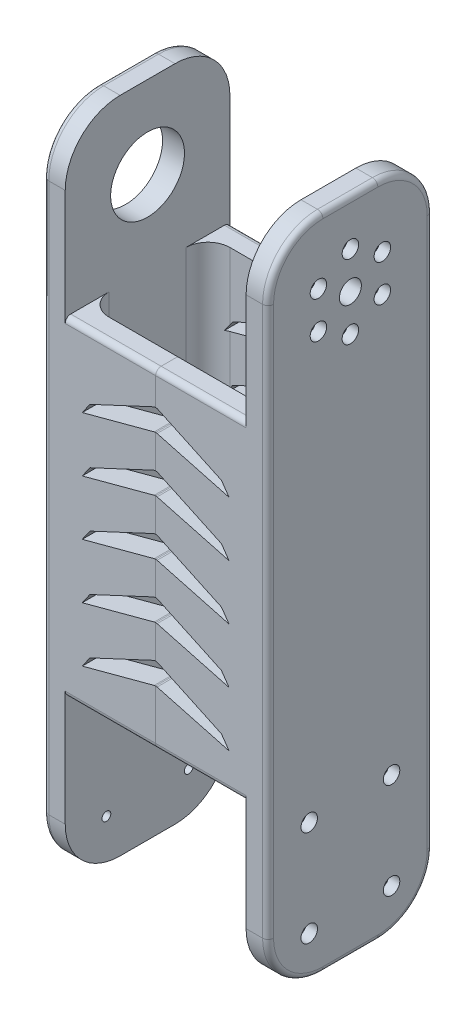
SolidWorks part; units mm, degrees
material "PETG-CF"
ref_plane "前视基准面" through (0, 0, 0) normal (0, 0, 1) x (1, 0, 0)
ref_plane "上视基准面" through (0, 0, 0) normal (0, 1, 0) x (1, 0, 0)
ref_plane "右视基准面" through (0, 0, 0) normal (1, 0, 0) x (0, 0, -1)
other "Configuration Table"
sketch "草图1" plane through (0, 0, 0) normal (1, 0, 0) x (0, 0, -1)
  line L1 (30, -120) -> (-30, -120)
  line L2 (30, -120) -> (30, 120)
  line L3 (30, 120) -> (-30, 120)
  line L4 (-30, -120) -> (-30, 120)
  line L5 (30, -120) -> (-30, 120) construction
  line L6 (30, 120) -> (-30, -120) construction
  point P0 (0, 0)
  dimension "D1" = 240
  dimension "D2" = 60
extrude "凸台-拉伸1" add sketch "草图1" along normal blind 8
sketch "草图2" plane through (8, 0, 0) normal (1, 0, 0) x (0, 0, -1)
  line L1 (30, 120) -> (-30, 120) construction
  circle A12 centre (0, 90) radius 13.45
  point P6 (0, 120)
  point P26 (0, 90)
  dimension "D11" = 26.9
  dimension "D2" = 30
extrude "切除-拉伸1" cut sketch "草图2" against normal through all
sketch "草图3" plane through (8, 0, 0) normal (1, 0, 0) x (0, 0, -1)
  line L0 (-30, 120) -> (-30, -120) construction
  line L1 (-22, -60) -> (-30, -60)
  line L2 (-22, -60) -> (-22, 60)
  line L3 (-22, 60) -> (-30, 60)
  line L4 (-30, -60) -> (-30, 60)
  line L5 (-22, -60) -> (-30, 60) construction
  line L6 (-22, 60) -> (-30, -60) construction
  line L7 (30, -60) -> (22, -60)
  line L8 (30, -60) -> (30, 60)
  line L9 (30, 60) -> (22, 60)
  line L10 (22, -60) -> (22, 60)
  line L11 (30, -60) -> (22, 60) construction
  line L12 (30, 60) -> (22, -60) construction
  line L13 (30, -120) -> (30, 120) construction
  line L14 (30, 120) -> (-30, 120) construction
  line L15 (-30, -120) -> (30, -120) construction
  point P0 (-26, 0)
  point P5 (26, 0)
  dimension "D1" = 60
  dimension "D2" = 60
  dimension "D3" = 60
  dimension "D4" = 60
  dimension "D5" = 8
  dimension "D6" = 8
extrude "凸台-拉伸2" add sketch "草图3" along normal blind 65.9
sketch "草图4" plane through (73.9, 0, 0) normal (1, 0, 0) x (0, 0, -1)
  line L0 (30, -120) -> (-30, 120) construction
  line L1 (30, -120) -> (-30, -120)
  line L2 (30, -120) -> (30, 120)
  line L3 (30, 120) -> (-30, 120)
  line L4 (-30, -120) -> (-30, 120)
  line L5 (30, -120) -> (-30, 120) construction
  line L6 (30, 120) -> (-30, -120) construction
  line L7 (30, 120) -> (-30, 120) construction
  point P0 (0, 0)
extrude "凸台-拉伸3" add sketch "草图4" along normal blind 8
fillet "圆角1" radius 20 8 edges at (4, -120, 30) (4, -120, -30) (4, 120, -30) (4, 120, 30) (77.9, 120, -30) (77.9, 120, 30) (77.9, -120, -30) (77.9, -120, 30)
sketch "草图9" plane through (73.9, 0, 0) normal (-1, 0, 0) x (0, 0, 1)
  circle A0 centre (0, 90) radius 19 construction
  circle A2 centre (0, 109) radius 1.6
  circle A3 centre (19, 90) radius 1.6
  circle A4 centre (0, 71) radius 1.6
  circle A5 centre (-19, 90) radius 1.6
  point P14 (0, 90)
  dimension "D1" = 38
  dimension "D2" = 3.2
sketch "草图10" plane through (81.9, 0, 0) normal (1, 0, 0) x (0, 0, -1)
  circle A0 centre (0, 90) radius 4
  circle A1 centre (0, 90) radius 13.5 construction
  circle A2 centre (0, 103.5) radius 1.6
  circle A3 centre (11.6913, 96.75) radius 1.6
  circle A4 centre (11.6913, 83.25) radius 1.6
  circle A5 centre (0, 76.5) radius 1.6
  circle A6 centre (-11.6913, 83.25) radius 1.6
  circle A7 centre (-11.6913, 96.75) radius 1.6
  point P18 (0, 90)
  dimension "D1" = 8
  dimension "D2" = 27
  dimension "D3" = 3.2
  dimension "D4" = 6
extrude "切除-拉伸2" cut sketch "草图10" against normal up to next
sketch "草图15" plane through (73.9, 0, 0) normal (-1, 0, 0) x (0, 0, 1)
  circle A0 centre (0, 90) radius 18
  dimension "D1" = 36
extrude "凸台-拉伸4" add sketch "草图15" along normal blind 9.8
sketch "草图11" plane through (81.9, 0, 0) normal (1, 0, 0) x (0, 0, -1)
  line L1 (15, -105) -> (-15, -105) construction
  line L2 (15, -105) -> (15, -70) construction
  line L3 (15, -70) -> (-15, -70) construction
  line L4 (-15, -105) -> (-15, -70) construction
  line L5 (15, -105) -> (-15, -70) construction
  line L6 (15, -70) -> (-15, -105) construction
  line L7 (-30, 100) -> (-30, -100) construction
  line L8 (30, -100) -> (30, 100) construction
  line L9 (0, -70) -> (0, -105) construction
  line L10 (-15, -87.5) -> (15, -87.5) construction
  line L11 (-22, -60) -> (-30, -60) construction
  circle A0 centre (-15, -70) radius 1.6
  circle A1 centre (15, -70) radius 1.6
  circle A2 centre (15, -105) radius 1.6
  circle A3 centre (-15, -105) radius 1.6
  point P0 (0, -87.5)
  dimension "D5" = 3.2
  dimension "D1" = 10
  dimension "D2" = 15
  dimension "D3" = 15
  dimension "D4" = 35
extrude "切除-拉伸3" cut sketch "草图11" against normal through all
sketch "草图12" plane through (81.9, 0, 0) normal (1, 0, 0) x (0, 0, -1)
  circle A0 centre (0, 103.45) radius 3
  circle A1 centre (0, 90) radius 13.45 construction
  circle A2 centre (11.648, 96.725) radius 3
  circle A3 centre (11.648, 83.275) radius 3
  circle A4 centre (0, 76.55) radius 3
  circle A5 centre (-11.648, 83.275) radius 3
  circle A6 centre (-11.648, 96.725) radius 3
  point P16 (0, 90)
  dimension "D1" = 6
  dimension "D2" = 6
extrude "切除-拉伸4" cut sketch "草图12" against normal blind 4
sketch "草图13" plane through (81.9, 0, 0) normal (1, 0, 0) x (0, 0, -1)
  line L2 (0, -70) -> (0, -105) construction
  line L3 (-15, -87.5) -> (15, -87.5) construction
  circle A0 centre (-15, -70) radius 3
  circle A1 centre (15, -70) radius 3
  circle A2 centre (15, -105) radius 3
  circle A3 centre (-15, -105) radius 3
  dimension "D1" = 6
extrude "切除-拉伸5" cut sketch "草图13" against normal blind 4
sketch "草图14" plane through (0, 0, 0) normal (-1, 0, 0) x (0, 0, 1)
  line L0 (0, -70) -> (0, -105) construction
  line L1 (-15, -87.5) -> (15, -87.5) construction
  circle A0 centre (-15, -70) radius 3
  circle A1 centre (15, -70) radius 3
  circle A2 centre (15, -105) radius 3
  circle A3 centre (-15, -105) radius 3
  dimension "D1" = 6
extrude "切除-拉伸6" cut sketch "草图14" against normal blind 4
extrude "切除-拉伸7" cut sketch "草图10<2>" against normal up to next
sketch "草图10<2>" plane through (81.9, 0, 0) normal (1, 0, 0) x (0, 0, -1) same geometry as "草图10"
ref_plane "基准面1" through (40.95, 0, 0) normal (1, 0, 0) x (0, 0, -1)
fillet "圆角2" radius 8 4 edges at (8, 0, -22) (73.9, 0, -22) (8, 0, 22) (73.9, 0, 22)
fillet "圆角3" radius 2 20 edges at (40.95, -60, 30) (40.95, -60, -30) (40.95, 60, 30) (40.95, 60, -30) (0, -114.1421, -24.1421) (0, -120, 0) (0, -114.1421, 24.1421) (0, 0, 30) (0, 114.1421, 24.1421) (0, 120, 0) (0, 114.1421, -24.1421) (81.9, -114.1421, -24.1421) (81.9, -120, 0) (81.9, -114.1421, 24.1421) (81.9, 0, 30) (81.9, 114.1421, 24.1421) (81.9, 120, 0) (81.9, 114.1421, -24.1421) (0, 0, -30) (81.9, 0, -30)
sketch "草图16" plane through (0, 0, -30) normal (0, 0, -1) x (-1, 0, 0)
  line L0 (-41.7952, -32.2261) -> (-64.9, -43)
  line L1 (-40.95, 30.8) -> (-40.95, -30.8) construction
  line L2 (-64.9, -43) -> (-67.7016, -47)
  line L3 (-67.7016, -47) -> (-41.4676, -39.9706)
  line L4 (-40.4324, -39.9706) -> (-14.1984, -47)
  line L5 (-14.1984, -47) -> (-17, -43)
  line L6 (-17, -43) -> (-40.1048, -32.2261)
  line L7 (-2, -100) -> (-2, 100) construction
  line L8 (-73.9, -58) -> (-8, -58) construction
  arc A0 (-41.4676, -39.9706) -> (-40.4324, -39.9706) centre (-40.95, -41.9025) cw
  arc A1 (-41.7952, -32.2261) -> (-40.1048, -32.2261) centre (-40.95, -34.0387) cw
  point P17 (-40.95, -39.8319)
  point P20 (-40.95, -31.8319)
  dimension "D8" = 2
  dimension "D1" = 65
  dimension "D2" = 65
  dimension "D3" = 15
  dimension "D4" = 11
  dimension "D5" = 4
  dimension "D6" = 150
  dimension "D7" = 8
extrude "切除-拉伸8" cut sketch "草图16" against normal through all
pattern_linear "阵列(线性)1" count 5 spacing 20 along (0, 1, 0) of "切除-拉伸8"
split "分割1" trim tools "基准面1" bodies to split 128 resulting bodies 125 126
